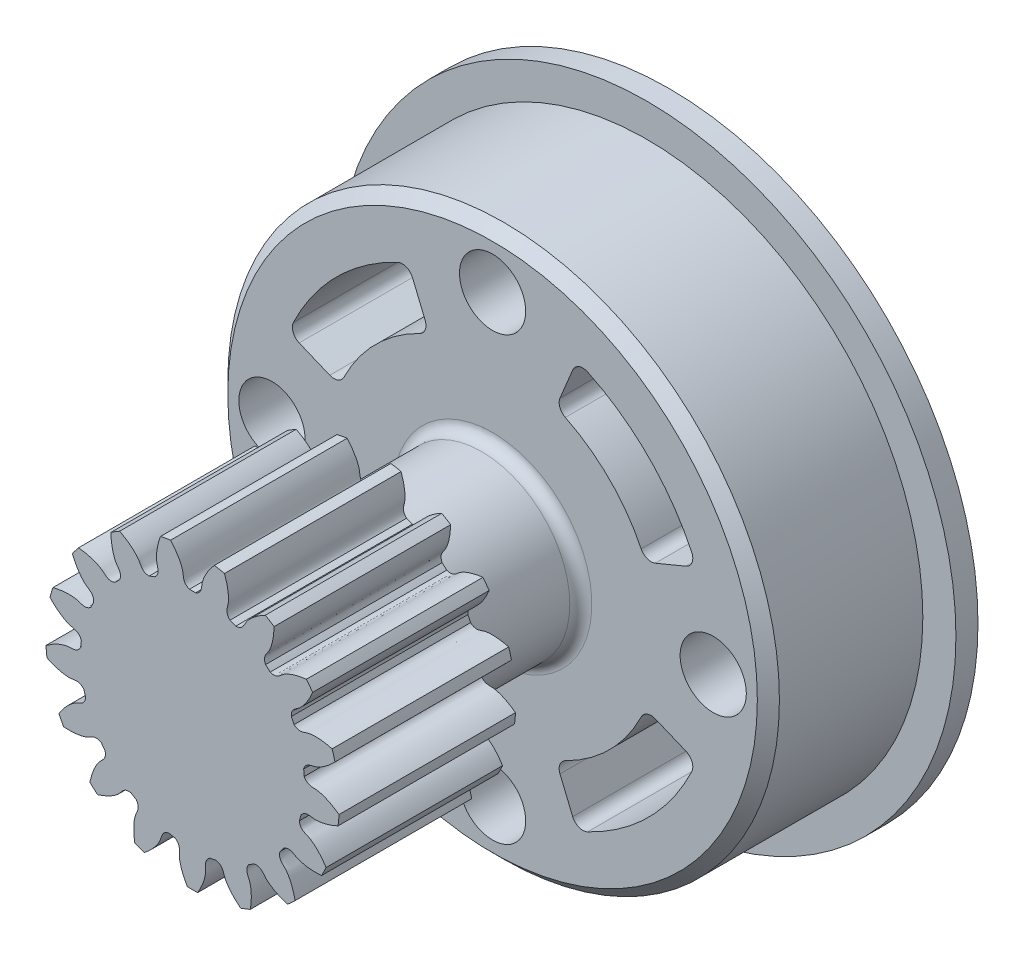
SolidWorks part; units mm, degrees
material "普通碳钢"
ref_plane "前视基准面" through (0, 0, 0) normal (0, 0, 1) x (1, 0, 0)
ref_plane "上视基准面" through (0, 0, 0) normal (0, 1, 0) x (1, 0, 0)
ref_plane "右视基准面" through (0, 0, 0) normal (1, 0, 0) x (0, 0, -1)
sketch "草图1" plane through (0, 0, 0) normal (0, 0, 1) x (1, 0, 0)
  circle A0 centre (0, 0) radius 6.65
extrude "凸台-拉伸1" add sketch "草图1" along normal blind 8
ref_axis "基准轴1" through (0, 0, -11.005) along (0, 0, 1)
sketch "草图2" plane through (0, 0, 0) normal (0, 0, 1) x (1, 0, 0)
  line L0 (0, 0) -> (0, 6.65) construction
  circle A0 centre (0, 0) radius 6.65 construction
  arc A1 (0.1412, 5.073) -> (-0.1412, 5.073) centre (0, 0) ccw
  arc A2 (2.181, 7.5185) -> (-2.181, 7.5185) centre (0, 0) ccw
  spline S0 degree 3 poles (0.1412, 5.073) (0.4395, 5.1974) (0.3963, 5.4284) (0.4468, 5.6454) (0.4515, 5.6638) (0.4571, 5.6843) (0.4638, 5.7068) (0.4716, 5.7313) (0.4806, 5.7578) (0.4909, 5.7862) (0.5026, 5.8164) (0.5157, 5.8485) (0.5303, 5.8824) (0.5466, 5.918) (0.5645, 5.9553) (0.5841, 5.9942) (0.6056, 6.0347) (0.629, 6.0767) (0.6544, 6.1202) (0.6817, 6.1651) (0.7112, 6.2113) (0.7428, 6.2587) (0.7767, 6.3074) (0.8128, 6.3572) (0.8513, 6.408) (0.8921, 6.4598) (0.9354, 6.5125) (0.9812, 6.566) (1.0296, 6.6203) (1.0805, 6.6753) (1.1341, 6.7308) (1.1904, 6.7868) (1.2494, 6.8432) (1.3112, 6.8999) (1.3757, 6.9569) (1.4431, 7.014) (1.5134, 7.0712) (1.5866, 7.1283) (1.6626, 7.1853) (1.7416, 7.2421) (1.8236, 7.2986) (1.9086, 7.3546) (2.0271, 7.4294) (2.1186, 7.4834) (2.181, 7.5185) knots 0 0 0 0 0.193883 0.199024 0.204851 0.211363 0.21856 0.226443 0.235011 0.244265 0.254205 0.264829 0.27614 0.288136 0.300817 0.314184 0.328236 0.342973 0.358397 0.374505 0.391299 0.408779 0.426944 0.445795 0.465331 0.485552 0.506459 0.528051 0.550329 0.573293 0.596941 0.621276 0.646296 0.672001 0.698392 0.725468 0.753229 0.781677 0.810809 0.840627 0.871131 0.90232 0.934195 1 1 1 1
  spline S1 degree 3 poles (-0.1412, 5.073) (-0.4395, 5.1974) (-0.3963, 5.4284) (-0.4468, 5.6454) (-0.4515, 5.6638) (-0.4571, 5.6843) (-0.4638, 5.7068) (-0.4716, 5.7313) (-0.4806, 5.7578) (-0.4909, 5.7862) (-0.5026, 5.8164) (-0.5157, 5.8485) (-0.5303, 5.8824) (-0.5466, 5.918) (-0.5645, 5.9553) (-0.5841, 5.9942) (-0.6056, 6.0347) (-0.629, 6.0767) (-0.6544, 6.1202) (-0.6817, 6.1651) (-0.7112, 6.2113) (-0.7428, 6.2587) (-0.7767, 6.3074) (-0.8128, 6.3572) (-0.8513, 6.408) (-0.8921, 6.4598) (-0.9354, 6.5125) (-0.9812, 6.566) (-1.0296, 6.6203) (-1.0805, 6.6753) (-1.1341, 6.7308) (-1.1904, 6.7868) (-1.2494, 6.8432) (-1.3112, 6.8999) (-1.3757, 6.9569) (-1.4431, 7.014) (-1.5134, 7.0712) (-1.5866, 7.1283) (-1.6626, 7.1853) (-1.7416, 7.2421) (-1.8236, 7.2986) (-1.9086, 7.3546) (-2.0271, 7.4294) (-2.1186, 7.4834) (-2.181, 7.5185) knots 0 0 0 0 0.193883 0.199024 0.204851 0.211363 0.21856 0.226443 0.235011 0.244265 0.254205 0.264829 0.27614 0.288136 0.300817 0.314184 0.328236 0.342973 0.358397 0.374505 0.391299 0.408779 0.426944 0.445795 0.465331 0.485552 0.506459 0.528051 0.550329 0.573293 0.596941 0.621276 0.646296 0.672001 0.698392 0.725468 0.753229 0.781677 0.810809 0.840627 0.871131 0.90232 0.934195 1 1 1 1
extrude "切除-拉伸1" cut sketch "草图2" along normal through all
pattern_circular "阵列(圆周)1" count 17 every 21.176 about axis through (0, 0, -11.005) along (0, 0, 1) of "切除-拉伸1"
sketch "草图3" plane through (0, 0, 0) normal (0, 0, 1) x (1, 0, 0)
  circle A0 centre (0, 0) radius 5.95 construction
  dimension "Dn" = 11.9
sketch "草图5" plane through (0, 0, 0) normal (1, 0, 0) x (0, 0, -1)
  line L0 (0, 0) -> (13.6, 0)
  line L1 (13.6, 0) -> (13.6, 14)
  line L2 (13.6, 14) -> (12.6, 14)
  line L3 (12.6, 14) -> (12.6, 12.5)
  line L4 (12.6, 12.5) -> (5.6, 12.5)
  line L5 (5.6, 12.5) -> (5.6, 4)
  line L6 (5.6, 4) -> (0, 4)
  line L8 (0, 4) -> (0, 0)
  dimension "D1" = 7
  dimension "D2" = 1
  dimension "D3" = 1.5
  dimension "D4" = 12.5
  dimension "D5" = 13.6
  dimension "D6" = 4
revolve "旋转1" add sketch "草图5" angle 360 about L0
sketch "草图6" plane through (0, 0, -5.6) normal (0, 0, 1) x (1, 0, 0)
  line L1 (0, 10) -> (-10, 0) construction
  line L2 (-10, 0) -> (0, -10) construction
  line L3 (0, -10) -> (10, 0) construction
  line L4 (10, 0) -> (0, 10) construction
  circle A0 centre (0, 0) radius 10 construction
  circle A1 centre (0, 10) radius 1.5
  circle A2 centre (10, 0) radius 1.5
  circle A3 centre (0, -10) radius 1.5
  circle A4 centre (-10, 0) radius 1.5
  dimension "D1" = 20
  dimension "D2" = 3
extrude "切除-拉伸2" cut sketch "草图6" against normal through all
sketch "草图7" plane through (0, 0, -13.6) normal (0, 0, -1) x (-1, 0, 0)
  circle A0 centre (0, 0) radius 3
  dimension "D1" = 6
extrude "切除-拉伸3" cut sketch "草图7" against normal blind 2.5
chamfer "倒角1" distance 0.5 angle 45 1 edges at (12.5, 0, -5.6)
fillet "圆角1" radius 0.5 2 edges at (4, 0, 0) (4, 0, -5.6)
sketch "草图8" plane through (0, 0, -5.6) normal (0, 0, 1) x (1, 0, 0)
  line L0 (-7.0711, 7.0711) -> (0, 0) construction
  line L1 (0, 0) -> (-9.2388, 3.8268) construction
  line L2 (-3.8268, 9.2388) -> (0, 0) construction
  line L3 (0, 10) -> (-10, 0) construction
  line L4 (-9.2388, 3.8268) -> (-6.9291, 2.8701)
  line L5 (-3.8268, 9.2388) -> (-2.8701, 6.9291)
  line L6 (9.2388, 3.8268) -> (6.9291, 2.8701)
  line L7 (3.8268, 9.2388) -> (2.8701, 6.9291)
  line L8 (3.8268, -9.2388) -> (2.8701, -6.9291)
  line L9 (9.2388, -3.8268) -> (6.9291, -2.8701)
  line L10 (-9.2388, -3.8268) -> (-6.9291, -2.8701)
  line L11 (-3.8268, -9.2388) -> (-2.8701, -6.9291)
  arc A0 (-6.9291, 2.8701) -> (-2.8701, 6.9291) centre (0, 0) cw
  arc A1 (-9.2388, 3.8268) -> (-3.8268, 9.2388) centre (0, 0) cw
  arc A2 (3.8268, 9.2388) -> (9.2388, 3.8268) centre (0, 0) cw
  arc A3 (2.8701, 6.9291) -> (6.9291, 2.8701) centre (0, 0) cw
  arc A4 (9.2388, -3.8268) -> (3.8268, -9.2388) centre (0, 0) cw
  arc A5 (6.9291, -2.8701) -> (2.8701, -6.9291) centre (0, 0) cw
  arc A6 (-3.8268, -9.2388) -> (-9.2388, -3.8268) centre (0, 0) cw
  arc A7 (-2.8701, -6.9291) -> (-6.9291, -2.8701) centre (0, 0) cw
  point P11 (-5, 5)
  point P27 (0, 0)
  dimension "D1" = 7.5
  dimension "D2" = 10
  dimension "D3" = 45
  dimension "D4" = 4
extrude "切除-拉伸4" cut sketch "草图8" against normal through all
fillet "圆角2" radius 0.5 16 edges at (-9.2388, 3.8268, -9.6) (-2.8701, 6.9291, -9.6) (-6.9291, 2.8701, -9.6) (3.8268, 9.2388, -9.6) (9.2388, 3.8268, -9.6) (6.9291, 2.8701, -9.6) (2.8701, 6.9291, -9.6) (9.2388, -3.8268, -9.6) (3.8268, -9.2388, -9.6) (2.8701, -6.9291, -9.6) (6.9291, -2.8701, -9.6) (-3.8268, -9.2388, -9.6) (-9.2388, -3.8268, -9.6) (-6.9291, -2.8701, -9.6) (-2.8701, -6.9291, -9.6) (-3.8268, 9.2388, -9.6)
